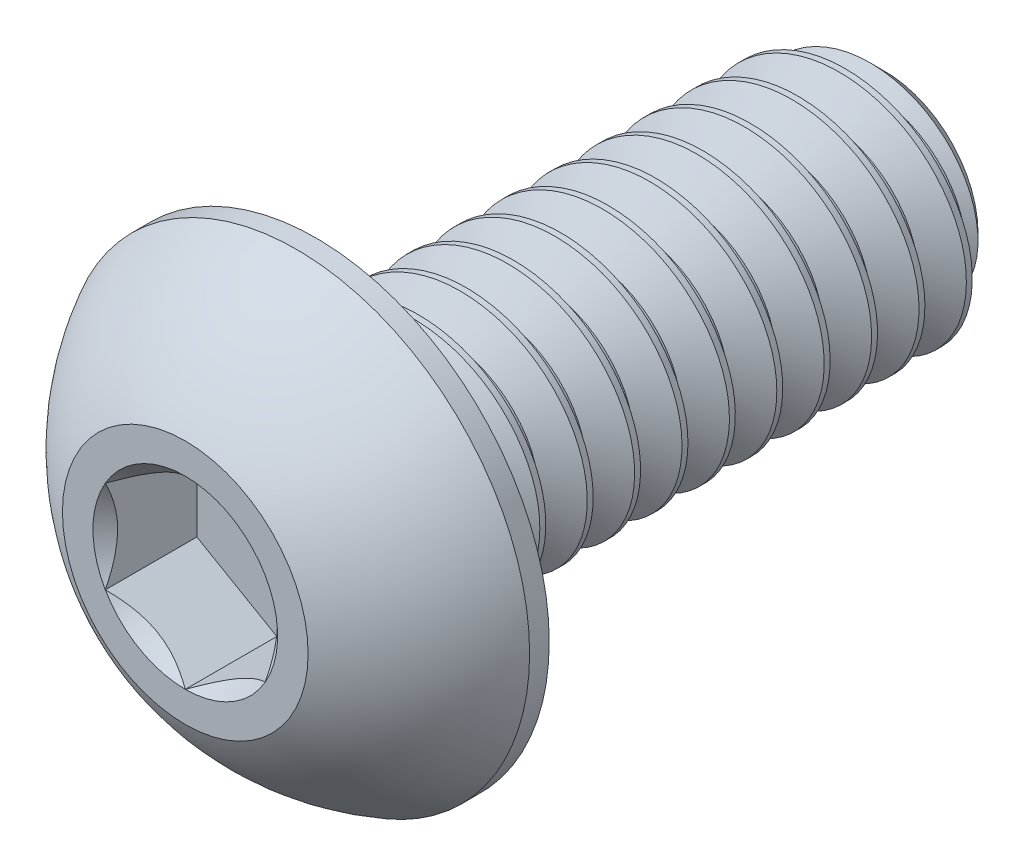
SolidWorks part; units mm, degrees
note: '?' marks a value the reader was unsure of.
ref_plane "Front" through (0, 0, 0) normal (0, 0, 1) x (1, 0, 0)
ref_plane "Top" through (0, 0, 0) normal (0, 1, 0) x (1, 0, 0)
ref_plane "Right" through (0, 0, 0) normal (1, 0, 0) x (0, 0, -1)
sketch "Sketch1" plane through (0, 0, 0) normal (1, 0, 0) x (0, 0, -1)
  line L2 (2.921, 2.7432) -> (15.621, 2.7432) construction
  line L3 (15.621, 2.7432) -> (15.621, 0) construction
  line L4 (15.621, 0) -> (2.921, 0) construction
  line L6 (2.4829, 5.207) -> (2.921, 5.207) construction
  line L7 (15.621, 2.7432) -> (15.621, -2.7432) construction
  line L8 (0, 0) -> (2.921, 0) construction
  line L9 (2.921, 5.207) -> (2.921, -5.207) construction
  line L11 (2.921, 2.7432) -> (2.921, 0) construction
  line L13 (0, 1.7859) -> (0, -1.7859) construction
  line L14 (0, 1.7859) -> (0, 2.7432) construction
  arc A3 (0, 2.7432) -> (2.4829, 5.207) centre (5.186, 0) cw construction
  point P10 (14.0335, -2.7432)
  point P16 (6.096, 0)
  point P19 (12.446, 0)
  dimension "D1" = 0.4381
  dimension "D2" = 1.5875
  dimension "D3" = 3.175
  dimension "D4" = 3.175
sketch "Sketch11" plane through (0, 0, 0) normal (1, 0, 0) x (0, 0, -1)
  line L1 (2.921, 0) -> (15.621, 0)
  line L4 (2.921, 2.7432) -> (15.621, 2.7432) construction
  line L5 (15.621, 2.7432) -> (15.621, 0) construction
  line L8 (2.921, 2.7432) -> (15.621, 2.7432)
  line L9 (15.621, 2.7432) -> (15.621, 0)
  line L10 (2.921, 2.7432) -> (2.921, 0)
revolve "Revolve1" add sketch "Sketch11" angle 360 about L1
chamfer "Chamfer1" distance 0.6615 angle 45 1 edges at (0, -2.7432, -15.621)
sketch "Sketch7" plane through (0, 0, 0) normal (1, 0, 0) x (0, 0, -1)
  line L6 (2.4829, 5.207) -> (2.921, 5.207) construction
  line L8 (0, 0) -> (2.921, 0) construction
  line L11 (2.921, 5.207) -> (2.921, -5.207) construction
  line L12 (2.4829, 5.207) -> (2.921, 5.207)
  line L13 (0, 0) -> (2.921, 0)
  line L14 (0, 1.7859) -> (0, -1.7859) construction
  line L15 (2.921, 5.207) -> (2.921, 0)
  line L16 (0, 2.7432) -> (0, 0)
  arc A2 (2.4829, 5.207) -> (0, 2.7432) centre (5.186, 0) ccw construction
  arc A3 (2.4829, 5.207) -> (0, 2.7432) centre (5.186, 0) ccw
revolve "Revolve2" add sketch "Sketch7" angle 360 mid plane about L13
sketch "Sketch5" plane through (0, 0, 0) normal (0, 0, 1) x (1, 0, 0)
  line L1 (1.7859, -1.0311) -> (1.7859, 1.0311)
  line L2 (1.7859, 1.0311) -> (0, 2.0622)
  line L3 (0, 2.0622) -> (-1.7859, 1.0311)
  line L4 (-1.7859, 1.0311) -> (-1.7859, -1.0311)
  line L5 (-1.7859, -1.0311) -> (0, -2.0622)
  line L6 (0, -2.0622) -> (1.7859, -1.0311)
  circle A0 centre (0, 0) radius 1.7859 construction
extrude "Cut-Extrude2" cut sketch "Sketch5" against normal blind 2.0447
sketch "Sketch6" plane through (0, 0, 0) normal (0, 0, 1) x (1, 0, 0)
  circle A0 centre (0, 0) radius 2.0622
extrude "Cut-Extrude3" cut sketch "Sketch6" against normal blind 2.0447 draft 45
sketch "Sketch3" plane through (0, 0, -15.621) normal (0, 0, -1) x (-1, 0, 0)
  circle A0 centre (0, 0) radius 2.7432
curve "Helix/Spiral1" pitch 1.0583 height 13.7583 turns 13
sketch "Sketch2" plane through (0, 0, 0) normal (1, 0, 0) x (0, 0, -1)
  line L0 (15.5549, 2.8578) -> (16.6132, 2.8578) construction
  line L1 (16.6132, 2.8578) -> (16.084, 1.9412) construction
  line L2 (16.084, 1.9412) -> (15.5549, 2.8578) construction
  line L3 (16.084, 1.9412) -> (16.084, 2.0558) construction
  line L4 (16.084, 2.0558) -> (16.084, 2.7432) construction
  line L5 (16.084, 2.7432) -> (16.084, 2.8578) construction
  line L6 (16.1502, 2.0558) -> (16.0179, 2.0558) construction
  line L7 (16.547, 2.7432) -> (15.621, 2.7432) construction
  line L8 (16.5801, 2.8005) -> (15.5879, 2.8005) construction
  line L9 (15.5879, 2.8005) -> (16.5801, 2.8005)
  line L10 (16.5801, 2.8005) -> (16.1502, 2.0558)
  line L11 (16.1502, 2.0558) -> (16.0179, 2.0558)
  line L12 (16.0179, 2.0558) -> (15.5879, 2.8005)
  line L13 (15.621, 2.7432) -> (2.921, 2.7432) construction
  line L14 (15.621, -2.7432) -> (15.621, 2.7432)
  line L15 (15.621, -2.7432) -> (15.621, 2.7432) construction
  line L16 (2.921, -5.207) -> (2.921, 5.207) construction
  point P10 (16.084, 2.0558)
  point P11 (16.084, 2.7432)
  point P16 (16.084, 2.8005)
  dimension "D1" = 1.0583
  dimension "D2" = 0.1323
sweep "Cut-Sweep1" cut profiles "Sketch2" path "Helix/Spiral1"
sketch "Sketch9" [suppressed] plane through (0, 0, -6.731) normal (0, 0, 1) x (1, 0, 0)
  circle A2 centre (0, 0) radius 6.35
extrude "Boss-Extrude2" [suppressed] add sketch "Sketch9" against normal offset from surface (57.15 mm away) 31.75
ref_axis "Center Axis 1" through (0, 0, -14.9595) along (0, 0, 1)?
ref_plane "Contact Plane 1" through (0, 0, -2.921) normal (0, 0, -1) x (-1, 0, 0)
ref_plane "Contact Plane 2" through (0, 0, -15.621) normal (0, 0, -1) x (-1, 0, 0)
equation "\"D3@Helix/Spiral1\" = \"Lg@Sketch1\" + \"D4@Helix/Spiral1\""
equation "\"D1@Chamfer1\"=\"D4@Helix/Spiral1\" * .625"
equation "\"D1@Cut-Extrude2\" = \"Head Ht@Sketch1\" * .7"
equation "\"D1@Sketch1\" = \"Head Ht@Sketch1\" * .15"
equation "\"D1@Cut-Extrude3\" = \"D1@Cut-Extrude2\""
equation "\"D2@Sketch1\"=\"D4@Helix/Spiral1\"*1.5"
equation "\"D3@Sketch1\"=\"Lg@Sketch1\"/4"
equation "\"D4@Sketch1\"=\"D3@Sketch1\""
equation "\"D1@Sketch2\"=\"D4@Helix/Spiral1\""
equation "\"D2@Sketch2\"=\"D1@Sketch2\"/8"
